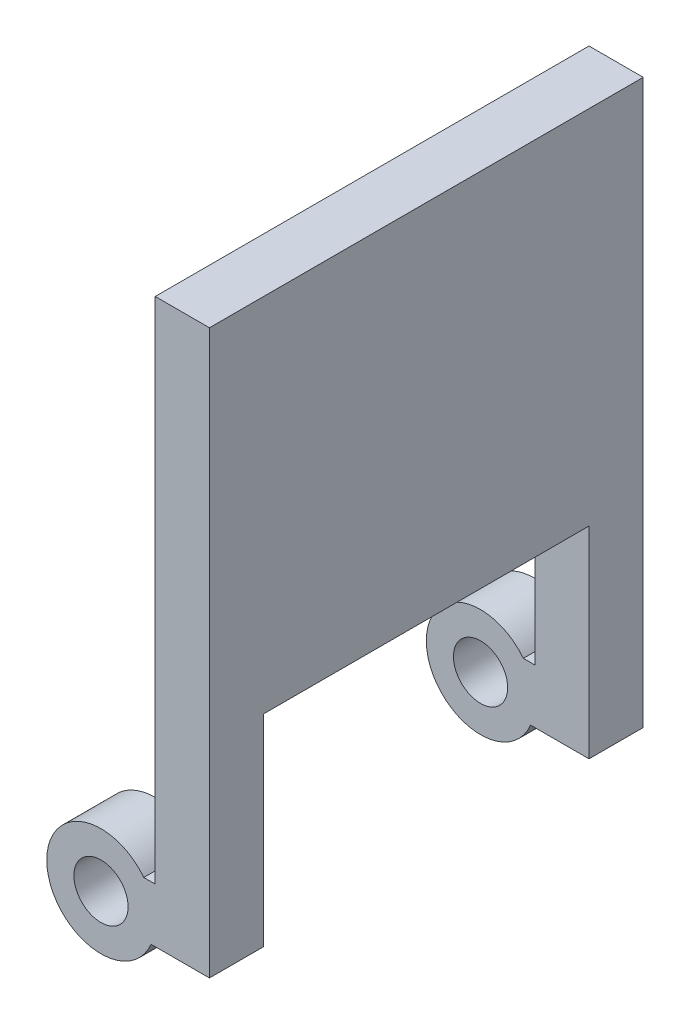
SolidWorks part; units mm, degrees
ref_plane "Front" through (0, 0, 0) normal (0, 0, 1) x (1, 0, 0)
ref_plane "Top" through (0, 0, 0) normal (0, 1, 0) x (1, 0, 0)
ref_plane "Right" through (0, 0, 0) normal (1, 0, 0) x (0, 0, -1)
sketch "Croquis1" plane through (0, 0, 0) normal (0, 0, 1) x (1, 0, 0)
  line L0 (0, 0) -> (0, 3) construction
  line L4 (0, 0) -> (9, 0) construction
  line L5 (9, 0) -> (9, 60) construction
  line L6 (9, 60) -> (6, 60)
  line L7 (6, 60) -> (6, 3.688)
  line L8 (6, 3.688) -> (4.7327, 3.688)
  line L9 (12, 54.8038) -> (12, 54.8038)
  line L10 (12, 54.8038) -> (12, -2.312)
  line L11 (12, -2.312) -> (5.5367, -2.312)
  line L12 (6, 3.688) -> (3, 3.688) construction
  line L13 (12, -2.312) -> (3, -2.312) construction
  line L14 (12, 54.8038) -> (12, 60)
  line L15 (12, 60) -> (9, 60)
  circle A0 centre (0, 0) radius 3
  arc A2 (4.7327, 3.688) -> (5.5367, -2.312) centre (0, 0) ccw
  dimension "D1" = 6
  dimension "D2" = 12
  dimension "D6" = 3
  dimension "D7" = 9
  dimension "D5" = 6
extrude "Saliente-Extruir1" add sketch "Croquis1" along normal blind 6
sketch "Croquis2" plane through (0, 0, 6) normal (0, 0, 1) x (1, 0, 0)
  line L1 (6, 60) -> (12, 60)
  line L2 (6, 60) -> (6, 20)
  line L3 (6, 20) -> (12, 20)
  line L4 (12, 60) -> (12, 20)
  point P5 (0, 0)
  point P6 (0, 0)
  point P7 (0, 0)
  dimension "D1" = 40
  dimension "D2" = 6
extrude "Saliente-Extruir2" add sketch "Croquis2" along normal blind 36
sketch "Croquis3" plane through (0, 0, 42) normal (0, 0, 1) x (1, 0, 0)
  line L3 (5.5367, -2.312) -> (12, -2.312)
  line L4 (12, -2.312) -> (12, 60)
  line L5 (12, 60) -> (6, 60)
  line L6 (6, 60) -> (6, 3.688)
  line L7 (6, 3.688) -> (4.7327, 3.688)
  circle A0 centre (0, 0) radius 3
  arc A2 (4.7327, 3.688) -> (5.5367, -2.312) centre (0, 0) ccw
  point P4 (0, 0)
  point P5 (0, 0)
extrude "Saliente-Extruir3" add sketch "Croquis3" along normal blind 6
